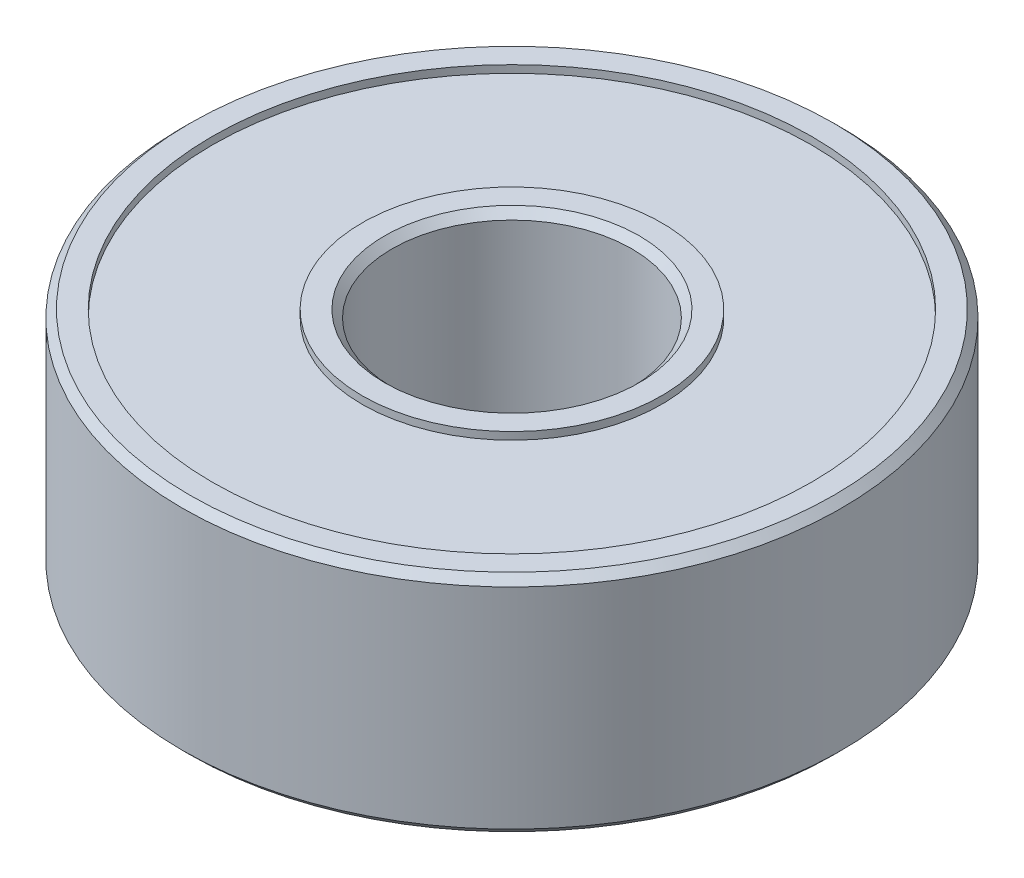
SolidWorks part; units mm, degrees
ref_plane "Front Plane" through (0, 0, 0) normal (0, 0, 1) x (1, 0, 0)
ref_plane "Top Plane" through (0, 0, 0) normal (0, 1, 0) x (1, 0, 0)
ref_plane "Right Plane" through (0, 0, 0) normal (1, 0, 0) x (0, 0, -1)
sketch "Sketch1" plane through (0, 0, 0) normal (0, 1, 0) x (1, 0, 0)
  circle A0 centre (0, 0) radius 4
  circle A1 centre (0, 0) radius 5
  circle A2 centre (0, 0) radius 11
  circle A3 centre (0, 0) radius 10
extrude "Extrude1" add sketch "Sketch1" along normal blind 3.75 and the other way blind 3.75 contours A2 A3 | A1 A0 region at (-4.8586, 0, 0) region at (-10.6889, 0, 0)
extrude "Extrude2" add sketch "Sketch1<4>" along normal blind 3.5 and the other way blind 3.5 separate body contours A3 A1 region at (-9.7172, 0, 0)
sketch "Sketch1<4>" plane through (0, 0, 0) normal (0, 1, 0) x (1, 0, 0) same geometry as "Sketch1"
chamfer "Chamfer1" distance 0.25 angle 45 1 edges at (0, 3.75, 11) tangent propagation no
chamfer "Chamfer2" distance 0.25 angle 45 1 edges at (0, -3.75, 11)
chamfer "Chamfer3" distance 0.25 angle 45 2 edges at (0, 3.75, 4) (0, -3.75, 4)
